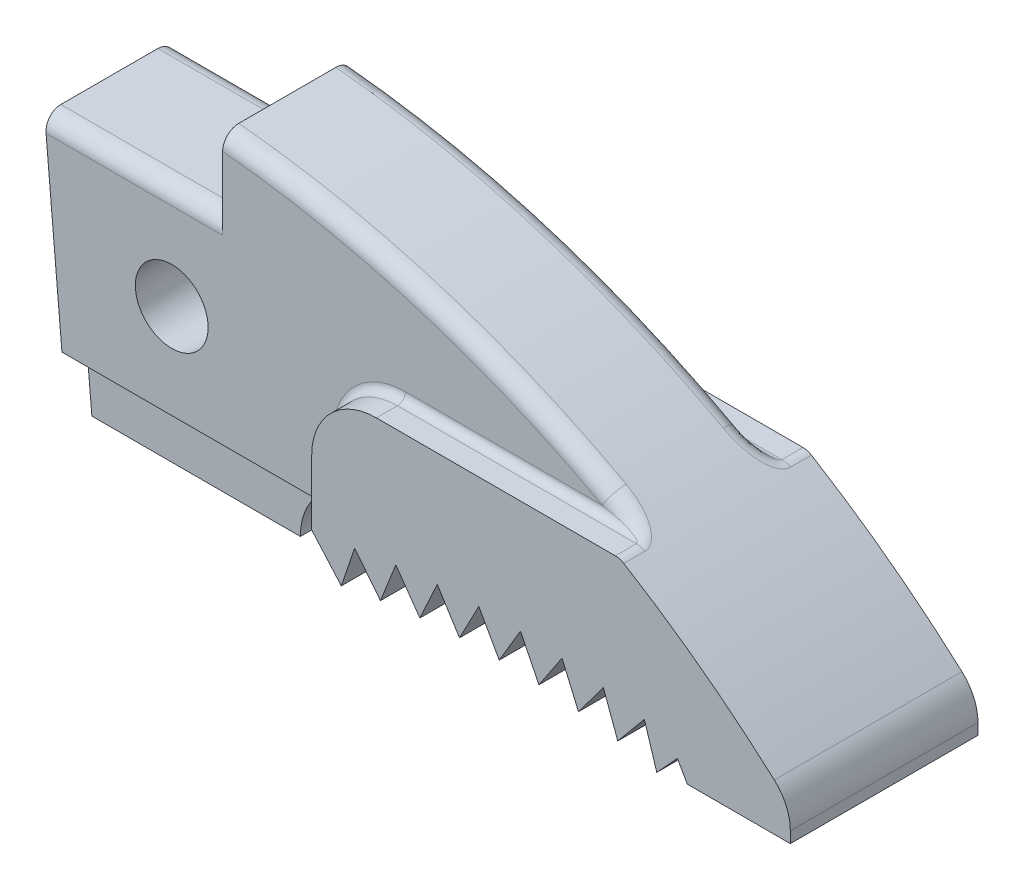
SolidWorks part; units mm, degrees
note: '?' marks a value the reader was unsure of.
ref_plane "Front Plane" through (0, 0, 0) normal (0, 0, 1) x (1, 0, 0)
ref_plane "Top Plane" through (0, 0, 0) normal (0, 1, 0) x (1, 0, 0)
ref_plane "Right Plane" through (0, 0, 0) normal (1, 0, 0) x (0, 0, -1)
sketch "Sketch1" plane through (0, 0, 0) normal (0, 0, 1) x (1, 0, 0)
  line L0 (0, 0) -> (0, 50.8039) construction
  line L1 (0, 0) -> (47.4869, 47.4869) construction
  line L2 (0, 0) -> (-4.2741, 48.8536) construction
  line L3 (-24.9861, 25.7175) -> (66.7901, 25.7175) construction
  line L4 (-3.459, 39.5365) -> (-2.25, 25.7175)
  line L5 (-2.25, 25.7175) -> (5.8796, 25.7175)
  line L6 (5.8796, 25.7175) -> (5.8796, 26.3525)
  line L7 (8.4196, 28.8925) -> (27.2088, 28.8925)
  circle A0 centre (0, 0) radius 39.6875 construction
  arc A1 (27.2088, 28.8925) -> (-3.459, 39.5365) centre (0, 0) ccw
  arc A2 (8.4196, 28.8925) -> (5.8796, 26.3525) centre (8.4196, 26.3525) ccw
  point P16 (5.8796, 28.8925)
  dimension "D1" = 79.375
  dimension "D4" = 13.97
  dimension "D8" = 2.54
  dimension "D2" = 45
  dimension "D3" = 5
  dimension "D5" = 5.8796
  dimension "D6" = 3.175
  dimension "D7" = 21.3292
extrude "Extrude1" add sketch "Sketch1" along normal mid plane 3.175
sketch "Sketch2" plane through (0, 0, 0) normal (0, 0, 1) x (1, 0, 0)
  line L0 (8.4196, 28.8925) -> (-2.5278, 28.8925)
  line L4 (-3.459, 39.5365) -> (-2.25, 25.7175)
  line L5 (-2.25, 25.7175) -> (5.8796, 25.7175)
  line L6 (5.8796, 25.7175) -> (5.8796, 26.3525)
  line L7 (8.4196, 28.8925) -> (27.2088, 28.8925)
  line L8 (-3.459, 39.5365) -> (-2.5278, 28.8925)
  line L11 (8.4196, 28.8925) -> (27.2088, 28.8925)
  arc A2 (27.2088, 28.8925) -> (-3.459, 39.5365) centre (0, 0) ccw
  arc A3 (8.4196, 28.8925) -> (5.8796, 26.3525) centre (8.4196, 26.3525) ccw
  arc A4 (27.2088, 28.8925) -> (-3.459, 39.5365) centre (0, 0) ccw
  dimension "D1" = 0
extrude "Extrude2" add sketch "Sketch2" along normal mid plane 5.08
sketch "Sketch3" plane through (0, 0, 0) normal (0, 0, 1) x (1, 0, 0)
  line L2 (27.2088, 28.8925) -> (8.4196, 28.8925)
  line L4 (20.5175, 33.9725) -> (8.4196, 33.9725)
  line L5 (8.4196, 28.8925) -> (8.4196, 33.9725)
  arc A0 (27.2088, 28.8925) -> (-3.459, 39.5365) centre (0, 0) ccw construction
  arc A1 (27.2088, 28.8925) -> (20.5175, 33.9725) centre (0, 0) ccw
  dimension "D1" = 5.08
extrude "Extrude3" add sketch "Sketch3" along normal mid plane 7.366
sketch "Sketch7" plane through (0, 0, 3.683) normal (0, 0, 1) x (1, 0, 0)
  line L0 (8.4196, 28.8925) -> (27.2088, 28.8925) construction
  line L1 (8.4196, 28.8925) -> (22.4336, 28.8925)
  arc A0 (8.4196, 28.8925) -> (22.4336, 28.8925) centre (15.4266, -1.6318) cw
  dimension "D1" = 31.3182
  dimension "D2" = 4.7752
extrude "Cut-Extrude1" cut sketch "Sketch7" against normal through all
sketch "Sketch4" plane through (0, 0, 0) normal (0, 0, 1) x (1, 0, 0)
  line L0 (8.4196, 28.8925) -> (9.5815, 27.5708)
  line L1 (9.5815, 27.5708) -> (10.1451, 29.2379)
  line L3 (9.5815, 27.5708) -> (9.2893, 29.0307) construction
  line L5 (8.4196, 33.9725) -> (8.4196, 28.8925) construction
  arc A1 (22.4336, 28.8925) -> (8.4196, 28.8925) centre (15.4266, -1.6318) ccw construction
  arc A2 (10.1451, 29.2379) -> (8.4196, 28.8925) centre (15.4266, -1.6318) ccw
  dimension "D1" = 30
  dimension "D2" = 30
  dimension "D4" = 1.7598
extrude "Extrude4" add sketch "Sketch4" along normal up to surface and the other way up to surface up to face at (17.4268, 31.1188, 3.683) other way up to face at (17.4268, 31.1188, -3.683)
ref_axis "Axis1" through (15.4266, -1.6318, 3.683) along (0, 0, -1)?
pattern_circular "CirPattern1" count 9 every 3 about axis through (15.4266, -1.6318, 0) along (0, 0, 1) of "Extrude4"
sketch "Sketch10" plane through (0, 0, 2.54) normal (0, 0, 1) x (1, 0, 0)
  line L1 (-7.2341, 44.5224) -> (3.7813, 44.5224)
  line L2 (-7.2341, 44.5224) -> (-7.2341, 36.6535)
  line L3 (-7.2341, 36.6535) -> (3.7813, 36.6535)
  line L4 (3.7813, 44.5224) -> (3.7813, 36.6535)
extrude "Cut-Extrude4" cut sketch "Sketch10" against normal through all
fillet "Fillet5" radius 2.54 2 edges at (8.4196, 33.9725, -3.1115) (8.4196, 33.9725, 3.1115)
fillet "Fillet4" radius 0.3175 6 edges at (15.7385, 33.9725, 2.54) (8.4196, 30.1625, 2.54) (8.4196, 30.1625, -2.54) (15.7385, 33.9725, -2.54) (9.1635, 33.2286, -2.54) (9.1635, 33.2286, 2.54)
fillet "Fillet6" radius 0.635 10 edges at (20.5175, 33.9725, 3.2702) (20.4507, 34.0128, 2.7028) (12.1648, 37.7772, 2.54) (20.5175, 33.9725, -3.2702) (20.4783, 33.9961, -2.7373) (2.9459, 28.8925, -1.5875) (2.9459, 28.8925, 1.5875) (12.1648, 37.7772, -2.54) (0.2873, 36.6535, -2.54) (0.2873, 36.6535, 2.54)
sketch "Sketch5" plane through (0, 28.8925, 0) normal (0, -1, 0) x (1, 0, 0)
  line L4 (22.4336, 3.683) -> (22.4336, -3.683)
  line L5 (22.4336, -3.683) -> (27.2088, -3.683)
  line L6 (27.2088, -3.683) -> (27.2088, 3.683)
  line L7 (27.2088, 3.683) -> (22.4336, 3.683)
  line L8 (22.4336, 3.683) -> (22.4336, -3.683)
  line L9 (22.4336, -3.683) -> (27.2088, -3.683)
  line L10 (27.2088, -3.683) -> (27.2088, 3.683)
  line L11 (27.2088, 3.683) -> (22.4336, 3.683)
  dimension "D1" = 0
extrude "Extrude5" add sketch "Sketch5" along normal blind 1.27
chamfer "Chamfer1" distance 1.27 angle 30 1 edges at (22.4336, 27.6225, 0)
fillet "Fillet7" radius 1.905 1 edges at (27.2088, 28.8925, 0)
sketch "Sketch9" plane through (5.8796, 0, 0) normal (1, 0, 0) x (0, 0, -1)
  line L4 (1.5875, 25.7175) -> (1.5875, 26.3525)
  line L5 (1.5875, 26.3525) -> (-1.5875, 26.3525)
  line L6 (-1.5875, 26.3525) -> (-1.5875, 25.7175)
  line L7 (-1.5875, 25.7175) -> (1.5875, 25.7175)
  line L8 (1.5875, 25.7175) -> (1.5875, 26.3525)
  line L9 (1.5875, 26.3525) -> (-1.5875, 26.3525)
  line L10 (-1.5875, 26.3525) -> (-1.5875, 25.7175)
  line L11 (-1.5875, 25.7175) -> (1.5875, 25.7175)
  dimension "D1" = 0
extrude "Cut-Extrude3" cut sketch "Sketch9" against normal through all
sketch "Sketch11" [suppressed] plane through (0, 0, -2.54) normal (0, 0, -1) x (-1, 0, 0)
  circle A0 centre (-2.54, 33.02) radius 1.8079
  dimension "D1" = 2.54
  dimension "D2" = 33.02
extrude "Cut-Extrude5" [suppressed] cut sketch "Sketch11" against normal blind 8.636
sketch "Sketch12" plane through (0, 0, -2.54) normal (0, 0, -1) x (-1, 0, 0)
  circle A0 centre (-1.7819, 32.6009) radius 1.4288
extrude "Cut-Extrude6" cut sketch "Sketch12" against normal blind 7.62
